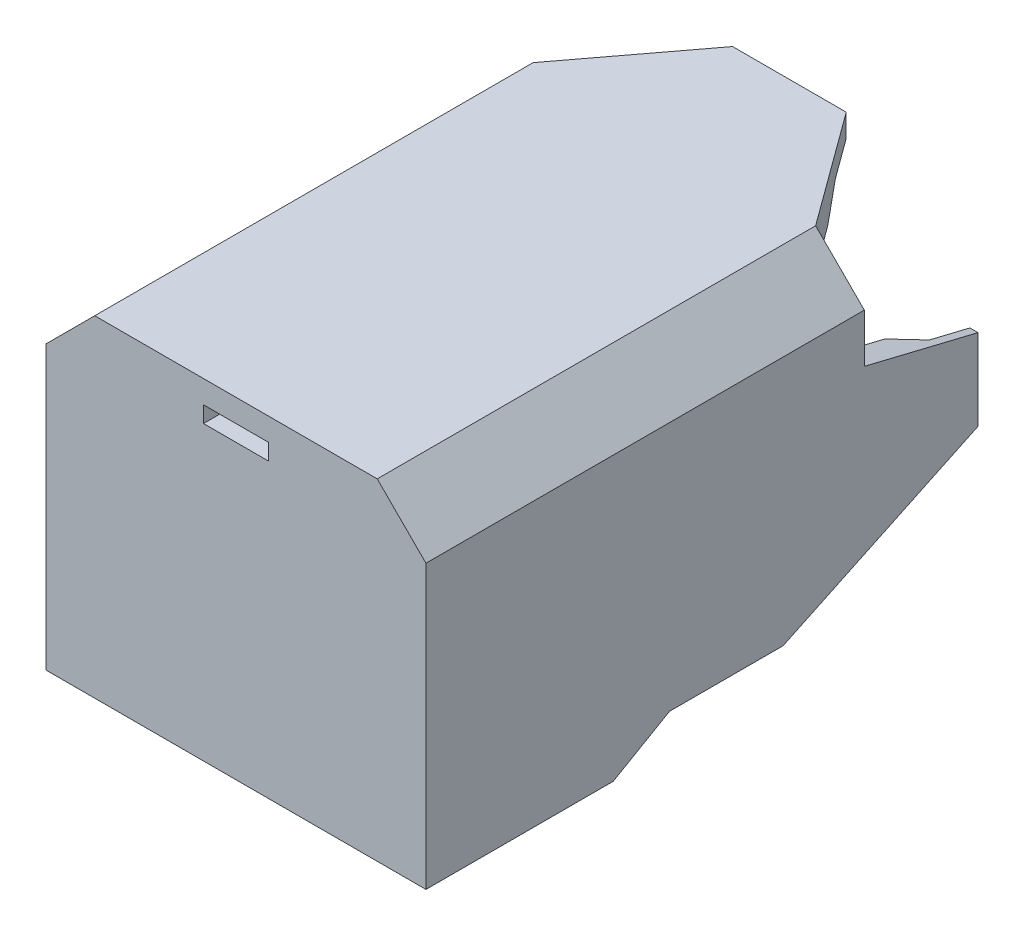
SolidWorks part; units mm, degrees
ref_plane "前视基准面" through (0, 0, 0) normal (0, 0, 1) x (1, 0, 0)
ref_plane "上视基准面" through (0, 0, 0) normal (0, 1, 0) x (1, 0, 0)
ref_plane "右视基准面" through (0, 0, 0) normal (1, 0, 0) x (0, 0, -1)
other "Configuration Table"
sketch "草图1" plane through (0, 0, 0) normal (0, 0, 1) x (1, 0, 0)
  line L0 (-11.7, 11.7) -> (11.7, -11.7) construction
  line L1 (-11.7, 11.7) -> (11.7, 11.7)
  line L2 (-11.7, 11.7) -> (-11.7, -11.7)
  line L3 (-11.7, -11.7) -> (11.7, -11.7)
  line L4 (11.7, 11.7) -> (11.7, -11.7)
  line L5 (11.7, 11.7) -> (-11.7, -11.7) construction
  line L7 (-10.2, 9.3) -> (10.2, 9.3)
  line L8 (-10.2, 9.3) -> (-10.2, -7.7)
  line L9 (-10.2, -7.7) -> (10.2, -7.7)
  line L10 (10.2, 9.3) -> (10.2, -7.7)
  line L15 (-5.1, 5.1) -> (5.1, -5.1) construction
  line L16 (-5.1, 5.1) -> (5.1, 5.1)
  line L17 (-5.1, 5.1) -> (-5.1, -5.1)
  line L18 (-5.1, -5.1) -> (5.1, -5.1)
  line L19 (5.1, 5.1) -> (5.1, -5.1)
  line L20 (5.1, 5.1) -> (-5.1, -5.1) construction
  point P4 (0, 0)
  point P14 (0, 0)
  dimension "D1" = 23.4
  dimension "D2" = 20.4
  dimension "D3" = 17
  dimension "D4" = 10.2
  dimension "D5" = 1.5
  dimension "D6" = 2.4
  dimension "D7" = 10.2
extrude "凸台-拉伸1" add sketch "草图1" against normal blind 38 contours L2 L3 L4 L1
extrude "切除-拉伸1" cut sketch "草图1<3>" against normal through all from offset 4.6 contours L7 L10 L9 L8 offset against normal yes
sketch "草图1<3>" plane through (0, 0, 0) normal (0, 0, 1) x (1, 0, 0) same geometry as "草图1"
extrude "切除-拉伸2" cut sketch "草图1<4>" against normal through all from offset 1 contours L16 L19 L18 L17 offset against normal yes
sketch "草图1<4>" plane through (0, 0, 0) normal (0, 0, 1) x (1, 0, 0) same geometry as "草图1"
chamfer "倒角2" distance 3 angle 45 2 edges at (-11.7, 11.7, -19) (11.7, 11.7, -19)
sketch "草图4" plane through (11.7, 0, 0) normal (1, 0, 0) x (0, 0, -1)
  line L1 (38, 8.7) -> (38, -11.7) construction
  line L2 (38, -11.7) -> (0, -11.7) construction
  line L3 (38, -11.7) -> (0, -11.7)
  line L4 (0, -11.7) -> (0, -8.7)
  line L5 (0, 8.7) -> (0, -11.7) construction
  line L6 (0, -8.7) -> (15, -8.7)
  line L7 (15, -8.7) -> (15, -6.7) construction
  line L8 (15, -6.7) -> (22, -6.7)
  line L9 (22, -6.7) -> (34, -1)
  line L10 (34, -1) -> (34, 4)
  line L11 (34, 4) -> (27, 5.7)
  line L12 (27, 5.7) -> (27, 8.7)
  line L13 (15, -6.7) -> (11.5359, -8.7)
  line L14 (27, 8.7) -> (38, 8.7)
  line L17 (38, 8.7) -> (38, -11.7)
  line L18 (25.6, -1) -> (39.75, -1) construction
  line L20 (38, 8.7) -> (0, 8.7) construction
  line M4 (38, -11.7) -> (38, 8.7)
  line M6 (0, 8.7) -> (0, -11.7)
  line M7 (0, -11.7) -> (38, -11.7)
  line M19 (38, 8.7) -> (0, 8.7)
  dimension "D1" = 15
  dimension "D2" = 3
  dimension "D3" = 2
  dimension "D4" = 7
  dimension "D5" = 5
  dimension "D6" = 3
  dimension "D7" = 11
  dimension "D8" = 4
  dimension "D9" = 30
extrude "切除-拉伸3" cut sketch "草图4" against normal through all contours L7 L6 L12 L11 L10 L9 L8 M6 M7 M4 M19 | L6 L7 L13 region at (11.7, -5.0851, -26.3749) region at (11.7, -8.0333, -13.8453)
sketch "草图5" plane through (0, 11.7, 0) normal (0, 1, 0) x (1, 0, 0)
  line L0 (-11.7, 27) -> (-8.7, 27)
  line L1 (-8.7, 27) -> (-3.4148, 34)
  line L2 (-3.4148, 34) -> (3.5852, 34)
  line L3 (3.5852, 34) -> (8.7, 27)
  line L4 (8.7, 0) -> (8.7, 38) construction
  line L5 (8.7, 27) -> (11.7, 27)
  line L6 (11.7, 27) -> (11.7, 38)
  line L7 (11.7, 38) -> (-11.7, 38)
  line L8 (-11.7, 38) -> (-11.7, 27)
  line L9 (-8.7, 38) -> (8.7, 38) construction
  line L10 (-11.7, 38) -> (-11.7, 27) construction
  point P17 (0, 38)
  dimension "D1" = 11
  dimension "D2" = 4
  dimension "D3" = 7
extrude "切除-拉伸4" cut sketch "草图5" against normal up to next
sketch "草图6" plane through (11.7, 0, 0) normal (1, 0, 0) x (0, 0, -1)
  line L0 (29.7679, 9.3) -> (31.5, 10.3)
  line L1 (34, 9.3) -> (27, 9.3) construction
  line L4 (34, 9.3) -> (29.7679, 9.3)
  line L5 (31.5, 10.3) -> (34, 10.3)
  line L6 (34, 9.3) -> (34, 11.7) construction
  line L7 (34, 10.3) -> (34, 9.3)
  dimension "D1" = 30
  dimension "D2" = 1
  dimension "D3" = 2.5
extrude "切除-拉伸5" cut sketch "草图6" against normal through all
sketch "草图7" plane through (0, 11.7, 0) normal (0, 1, 0) x (1, 0, 0)
  line L0 (-11.2, 34) -> (-10.2, 34)
  line L1 (-11.7, 34) -> (-10.2, 34) construction
  line L2 (-10.2, 34) -> (-10.2, 27) construction
  line L3 (-10.2, 34) -> (-10.2, 29.7679)
  line L4 (-10.2, 29.7679) -> (-11.2, 31.5)
  line L5 (-11.2, 31.5) -> (-11.2, 34)
  line L6 (10.2, 34) -> (10.2, 29.7679)
  line L7 (10.2, 34) -> (10.2, 27) construction
  line L8 (10.2, 29.7679) -> (11.2, 31.5)
  line L9 (11.2, 31.5) -> (11.2, 34)
  line L10 (10.2, 34) -> (11.7, 34) construction
  line L11 (11.2, 34) -> (10.2, 34)
  dimension "D1" = 30
  dimension "D2" = 1
  dimension "D3" = 2.5
extrude "切除-拉伸6" cut sketch "草图7" against normal through all
sketch "草图10" plane through (0, 0, 0) normal (0, 0, 1) x (1, 0, 0)
  line L0 (-8.7, 11.7) -> (8.7, 11.7) construction
  line L1 (-2, 10.3) -> (2, 10.3)
  line L2 (-2, 10.3) -> (-2, 9.3)
  line L3 (-2, 9.3) -> (2, 9.3)
  line L4 (2, 10.3) -> (2, 9.3)
  line L5 (0, 11.7) -> (0, 9.3) construction
  dimension "D1" = 2.4
  dimension "D2" = 4
  dimension "D3" = 1
extrude "切除-拉伸10" cut sketch "草图10" against normal blind 12
sketch "草图11" plane through (0, -8.7, 0) normal (0, -1, 0) x (1, 0, 0)
  line L0 (11.7, 0) -> (-11.7, 0) construction
  line L1 (0, 0) -> (0, -2.3) construction
  point P0 (0, 0)
  dimension "D1" = 2.3
hole_wizard "孔1" positions "草图12" profile "草图13" legacy end condition up to next
sketch "草图12" plane through (0, -8.7, 0) normal (0, -1, 0) x (-1, 0, 0)
  point P0 (0, 2.3)
sketch "草图13" plane through (0, -8.7, -2.3) normal (1, 0, 0) x (0, 0, -1)
  line L0 (0, 0) -> (0, 3.6)
  line L1 (0, 3.6) -> (0.9, 3.6)
  line L2 (0.9, 3.6) -> (0.9, 0)
  line L3 (0.9, 0) -> (0, 0)
  line L4 (0, 110) -> (0, -10) construction
  dimension "直径" = 1.8
  dimension "深度" = 3.6
